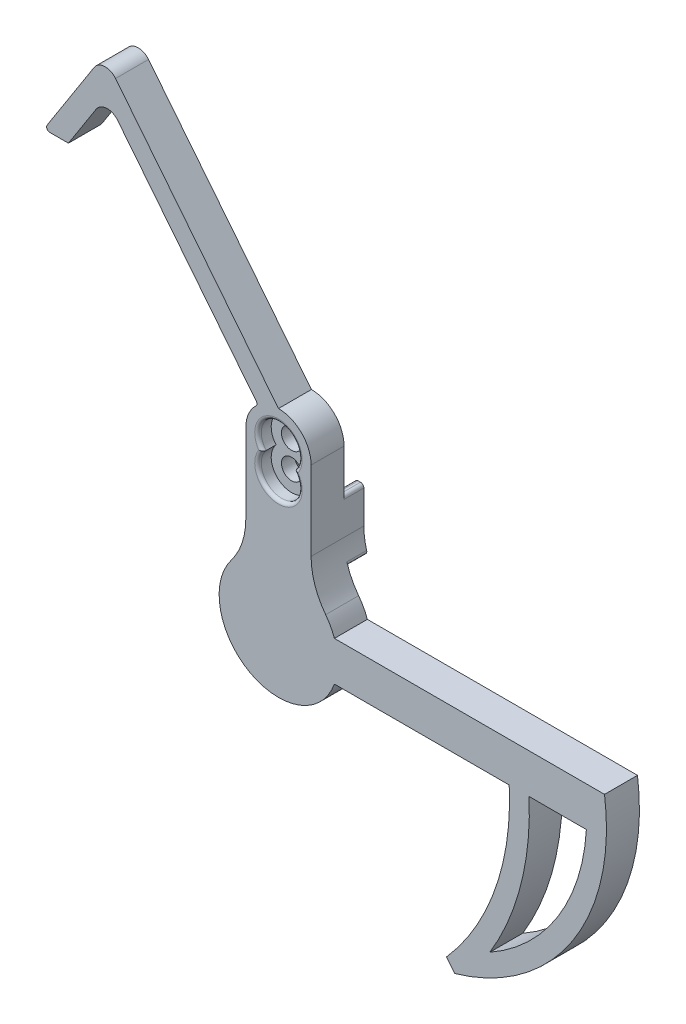
SolidWorks part; units mm, degrees
material "PLA"
ref_plane "Front Plane" through (0, 0, 0) normal (0, 0, 1) x (1, 0, 0)
ref_plane "Top Plane" through (0, 0, 0) normal (0, 1, 0) x (1, 0, 0)
ref_plane "Right Plane" through (0, 0, 0) normal (1, 0, 0) x (0, 0, -1)
sketch "Sketch1" plane through (0, 0, 0) normal (0, 0, 1) x (1, 0, 0)
  line L0 (-15.8075, -15.8075) -> (15.8075, 15.8075) construction
  line L1 (-15.8075, 15.8075) -> (15.8075, -15.8075) construction
  line L2 (0, 0) -> (0, 22.3552) construction
  line L3 (-3.5028, 12) -> (-3.35, 24)
  line L4 (-4.95, 12) -> (-4.95, 24)
  line L5 (4.95, 12) -> (4.95, 24)
  line L6 (3.5028, 12) -> (3.35, 24)
  line L9 (0.65, -3.8962) -> (0.65, -7.1706)
  line L10 (3.15, 12) -> (3.15, 24)
  line L11 (-3.15, 24) -> (-3.15, 12)
  line L12 (-0.65, -7.1706) -> (-0.65, -3.8962)
  line L13 (-0.65, 3.8962) -> (-0.65, 7.6481)
  line L14 (0.65, 7.6481) -> (0.65, 3.8962)
  line L15 (0.65, -3.8962) -> (0.65, -7.1706) construction
  line L16 (3.15, 12) -> (3.15, 24) construction
  line L17 (-3.15, 24) -> (-3.15, 12) construction
  line L18 (-0.65, -7.1706) -> (-0.65, -3.8962) construction
  line L19 (-0.65, 3.8962) -> (-0.65, 7.6481) construction
  line L20 (0.65, 7.6481) -> (0.65, 3.8962) construction
  circle A0 centre (0, 0) radius 22.3552 construction
  circle A1 centre (0, 20) radius 1.55
  circle A2 centre (0, 24) radius 1.55
  arc A3 (1.4948, 8.875) -> (-1.4948, 8.875) centre (0, 0) ccw
  circle A4 centre (-15.7528, 12) radius 12.25 construction
  arc A5 (-4.1855, 7.9675) -> (-3.5028, 12) centre (-15.7528, 12) ccw
  arc A6 (3.35, 24) -> (-3.35, 24) centre (0, 24) ccw
  circle A7 centre (-15.7528, 12) radius 10.8028 construction
  arc A9 (-4.95, 12) -> (-7.1593, 5.4538) centre (-15.7528, 12) cw
  arc A11 (-4.95, 24) -> (4.95, 24) centre (0, 24) cw
  arc A12 (0.65, -7.1706) -> (5.7275, 4.363) centre (0, 0) ccw
  arc A13 (3.15, 12) -> (5.7275, 4.363) centre (15.7528, 12) ccw
  arc A14 (3.15, 24) -> (-3.15, 24) centre (0, 24) ccw
  arc A15 (-5.7275, 4.363) -> (-3.15, 12) centre (-15.7528, 12) ccw
  arc A16 (-5.7275, 4.363) -> (-0.65, -7.1706) centre (0, 0) ccw
  arc A17 (-0.65, 3.8962) -> (-0.65, -3.8962) centre (0, 0) ccw
  arc A18 (0.65, 7.6481) -> (-0.65, 7.6481) centre (0, 9) ccw
  arc A19 (0.65, -3.8962) -> (0.65, 3.8962) centre (0, 0) ccw
  arc A20 (0.65, -7.1706) -> (5.7275, 4.363) centre (0, 0) ccw construction
  arc A21 (3.15, 12) -> (5.7275, 4.363) centre (15.7528, 12) ccw construction
  arc A22 (3.15, 24) -> (-3.15, 24) centre (0, 24) ccw construction
  arc A23 (-5.7275, 4.363) -> (-3.15, 12) centre (-15.7528, 12) ccw construction
  arc A24 (-5.7275, 4.363) -> (-0.65, -7.1706) centre (0, 0) ccw construction
  arc A25 (-0.65, 3.8962) -> (-0.65, -3.8962) centre (0, 0) ccw construction
  arc A26 (0.65, 7.6481) -> (-0.65, 7.6481) centre (0, 9) ccw construction
  arc A27 (0.65, -3.8962) -> (0.65, 3.8962) centre (0, 0) ccw construction
  arc A29 (-7.1593, 5.4538) -> (7.1593, 5.4538) centre (0, 0) ccw
  circle A30 centre (0, 0) radius 7.7902
  arc A31 (-4.1855, 7.9675) -> (-5.1734, 5.8243) centre (21.9382, -5.373) ccw
  arc A32 (4.1855, 7.9675) -> (5.1734, 5.8243) centre (-21.9382, -5.373) cw
  arc A33 (4.1855, 7.9675) -> (3.5028, 12) centre (15.7528, 12) cw
  arc A34 (4.95, 12) -> (7.1593, 5.4538) centre (15.7528, 12) ccw
  dimension "D1" = 3.1
  dimension "D2" = 3.1
  dimension "D6" = 18
  dimension "D8" = 24.5
  dimension "D9" = 15.5803
  dimension "D3" = 4
  dimension "D4" = 20
  dimension "D5" = 45
  dimension "D7" = 0
extrude "Boss-Extrude1" add sketch "Sketch1" along normal blind 4 contours A2 | A1 | A9 A29 A34 L5 A11 L4 region at (0, 20, 0) region at (0, 24, 0)
extrude "Boss-Extrude2" add sketch "Sketch1<6>" against normal blind 1 contours A9 A29 A34 L5 A11 L4 A33 A32 A30 A31 A5 L3 A6 L6 region at (-4.53, 18, 0)
sketch "Sketch1<6>" plane through (0, 0, 0) normal (0, 0, 1) x (1, 0, 0) same geometry as "Sketch1"
sketch "Sketch2" plane through (0, 0, -1) normal (0, 0, -1) x (-1, 0, 0)
  line L0 (3.583, 17.483) -> (3.6529, 11.9938)
  line L1 (0, 0) -> (0, 24) construction
  line L2 (4.95, 12) -> (4.95, 24)
  line L3 (-4.95, 24) -> (-4.95, 12)
  line L4 (4.95, 12) -> (4.95, 24)
  line L5 (-4.95, 24) -> (-4.95, 12)
  line L6 (3.5028, 12) -> (3.35, 24)
  line L7 (-3.35, 24) -> (-3.5028, 12)
  line L8 (3.5028, 12) -> (3.35, 24) construction
  line L9 (-3.35, 24) -> (-3.5028, 12) construction
  line L10 (4.95, 17.5004) -> (3.583, 17.483)
  line L11 (4.2882, 8.1307) -> (5.5172, 8.5455)
  line L12 (-3.583, 17.483) -> (-3.6529, 11.9938)
  line L13 (-4.95, 17.5004) -> (-3.583, 17.483)
  line L14 (-4.2882, 8.1307) -> (-5.5172, 8.5455)
  circle A0 centre (15.7528, 12) radius 12.0999 construction
  arc A1 (4.2882, 8.1307) -> (3.6529, 11.9938) centre (15.7528, 12) cw
  arc A2 (-4.2882, 8.1307) -> (-3.6529, 11.9938) centre (-15.7528, 12) ccw
  arc A4 (4.95, 12) -> (7.1593, 5.4538) centre (15.7528, 12) ccw
  arc A5 (4.95, 24) -> (-4.95, 24) centre (0, 24) ccw
  arc A6 (-7.1593, 5.4538) -> (-4.95, 12) centre (-15.7528, 12) ccw
  arc A7 (-7.1593, 5.4538) -> (7.1593, 5.4538) centre (0, 0) ccw
  arc A8 (4.95, 12) -> (7.1593, 5.4538) centre (15.7528, 12) ccw
  arc A9 (4.95, 24) -> (-4.95, 24) centre (0, 24) ccw
  arc A10 (-7.1593, 5.4538) -> (-4.95, 12) centre (-15.7528, 12) ccw
  arc A11 (-7.1593, 5.4538) -> (7.1593, 5.4538) centre (0, 0) ccw
  arc A14 (-4.1855, 7.9675) -> (-3.5028, 12) centre (-15.7528, 12) ccw
  arc A15 (-4.1855, 7.9675) -> (-5.1734, 5.8243) centre (21.9382, -5.373) ccw
  arc A16 (-5.1734, 5.8243) -> (5.1734, 5.8243) centre (0, 0) ccw
  arc A17 (5.1734, 5.8243) -> (4.1855, 7.9675) centre (-21.9382, -5.373) ccw
  arc A18 (3.5028, 12) -> (4.1855, 7.9675) centre (15.7528, 12) ccw
  arc A19 (3.35, 24) -> (-3.35, 24) centre (0, 24) ccw
  arc A20 (-4.1855, 7.9675) -> (-3.5028, 12) centre (-15.7528, 12) ccw construction
  arc A21 (-4.1855, 7.9675) -> (-5.1734, 5.8243) centre (21.9382, -5.373) ccw construction
  arc A22 (-5.1734, 5.8243) -> (5.1734, 5.8243) centre (0, 0) ccw construction
  arc A23 (5.1734, 5.8243) -> (4.1855, 7.9675) centre (-21.9382, -5.373) ccw construction
  arc A24 (3.5028, 12) -> (4.1855, 7.9675) centre (15.7528, 12) ccw construction
  arc A25 (3.35, 24) -> (-3.35, 24) centre (0, 24) ccw construction
  arc M20 (7.1593, 5.4538) -> (4.95, 12) centre (15.7528, 12) cw
  line M21 (4.95, 12) -> (4.95, 24)
  arc M24 (-4.95, 12) -> (-7.1593, 5.4538) centre (-15.7528, 12) cw
  dimension "D3" = 0.15
  dimension "D4" = 5.5
  dimension "D1" = 0
  dimension "D2" = 0
extrude "Boss-Extrude3" add sketch "Sketch2" along normal blind 3 contours A1 L11 L10 L0 M20 M21 | L14 A2 L12 L13 L5 M24 region at (-4.3663, 12.9319, -1) region at (4.3663, 12.9319, -1)
sketch "Sketch3" plane through (0, 0, 4) normal (0, 0, 1) x (1, 0, 0)
  circle A0 centre (0, 24) radius 1.55 construction
  circle A1 centre (0, 20) radius 1.55 construction
  circle A2 centre (0, 24) radius 1.55
  circle A3 centre (0, 20) radius 1.55
  circle A4 centre (0, 20) radius 3.1
  circle A5 centre (0, 24) radius 3.1
  dimension "D1" = 6.2
  dimension "D2" = 6.2
extrude "Cut-Extrude1" cut sketch "Sketch3" against normal blind 2
fillet "Fillet2" radius 0.5 10 edges at (-3.583, 17.483, -2.5) (-4.95, 17.5004, -2.5) (3.583, 17.483, -2.5) (-5.5172, 8.5455, -2.5) (-4.2882, 8.1307, -2.5) (4.95, 17.5004, -2.5) (5.5172, 8.5455, -2.5) (4.2882, 8.1307, -2.5) (0, 27.1, 4) (0, 16.9, 4)
ref_plane "Plane1" through (0, 0, 5) normal (0, 0, 1) x (1, 0, 0)
sketch "Sketch4" plane through (0, 0, 4) normal (0, 0, 1) x (1, 0, 0)
  line L0 (0, 0) -> (34.7263, 0) construction
  line L1 (0, 0) -> (25.4725, -30.357) construction
  line L2 (25.4725, -30.357) -> (26.7581, -31.8891)
  line L3 (34.7263, 0) -> (49.7263, 0)
  line L4 (35, -3) -> (8.4853, -3)
  line L5 (35, 3) -> (8.4853, 3)
  line L6 (35, 3) -> (49.7263, 3)
  line L7 (49.7263, 3) -> (49.7263, 0)
  line L9 (38.0037, -3) -> (46.7056, -3)
  circle A0 centre (0, 0) radius 9
  arc A3 (34.7263, 0) -> (25.4725, -30.357) centre (-3.3379, -4.9858) cw
  arc A4 (49.7263, 0) -> (26.7581, -31.8891) centre (17.9508, -1.3297) cw
  circle A5 centre (17.9508, -1.3297) radius 31.8032 construction
  arc A6 (49.7263, 0) -> (49.458, 3) centre (17.9508, -1.3297) ccw
  circle A7 centre (17.9508, -1.3297) radius 28.8032 construction
  circle A8 centre (-3.3379, -4.9858) radius 41.3893 construction
  arc A9 (38.0037, -3) -> (32.0548, -26.4435) centre (-3.3379, -4.9858) cw
  arc A10 (46.7056, -3) -> (32.0548, -26.4435) centre (17.9508, -1.3297) cw
  point P20 (32.0548, -26.4435)
  arc M20 (-7.1593, 5.4538) -> (7.1593, 5.4538) centre (0, 0) ccw
  dimension "D1" = 18
  dimension "D2" = 35
  dimension "D4" = 6
  dimension "D8" = 18
  dimension "D9" = 3
  dimension "D10" = 3
  dimension "D3" = 2
  dimension "D5" = 15
  dimension "D6" = 50
  dimension "D7" = 3
extrude "Boss-Extrude4" add sketch "Sketch4" against normal up to surface (5 mm away) contours A3 L3 L7 L6 L5 L4 M20 | L3 A3 L2 L9 region at (33.2943, -17.7435, 4) region at (26.3516, 0.3286, 4) up to face at (0, 12.7161, -1)
sketch "Sketch5" plane through (0, 0, 4) normal (0, 0, 1) x (1, 0, 0)
  line L0 (0, 24) -> (-27.2138, 58.1477) construction
  line L1 (-27.2138, 58.1477) -> (-33.7931, 47.8777) construction
  line L2 (0, 28.95) -> (-26.4471, 62.1357)
  line L3 (-26.4471, 62.1357) -> (-35.5813, 47.8777)
  line L4 (-35.5813, 47.8777) -> (-33.7931, 47.8777)
  line L5 (-33.7931, 47.8777) -> (-31.8562, 47.8777)
  line L6 (-31.8562, 47.8777) -> (-26.14, 56.8004)
  line L7 (-26.14, 56.8004) -> (-3.085, 27.8711)
  arc A0 (4.95, 24) -> (-4.95, 24) centre (0, 24) ccw construction
  arc A1 (-3.085, 27.8711) -> (0, 28.95) centre (0, 24) cw
extrude "Boss-Extrude5" add sketch "Sketch5" against normal up to surface (5 mm away) up to face at (5.6426, 7.7752, -1)
fillet "Fillet3" radius 2 2 edges at (-26.14, 56.8004, 1.5) (-26.4471, 62.1357, 1.5)
fillet "Fillet4" radius 0.5 2 edges at (-35.5813, 47.8777, 1.5) (-3.085, 27.8711, 1.5)
equation "\"O_R\"= 4'Outer radius (Addendum)"
equation "\"I_R\"= 2.9'Inner radius (Dedendum)"
equation "\"N\"= 25'# of teeth"
equation "\"phi\"= 20'Pressure angle"
equation "\"P_R\"= 3'Pitch radius"
equation "\"a\"= ( \"period\" - ( \"err\" + \"T_F\" ) * ( \"I_R\" ) ) / ( 1 + ( \"O_R\" / \"I_R\" ) )'Outer arc degree"
equation "\"a_i\"= \"a\" * \"O_R\" / \"I_R\"'Inner arc degree (+manufacturing)"
equation "\"err\"= .03'Manufacturing error"
equation "\"period\"= 360 / \"N\"'Period of gear teeth"
equation "\"T_F\"= \"O_R\" / 2cm'Transition factor for curve"
equation "\"D4@Sketch19\"= \"a_i\" / 2"
